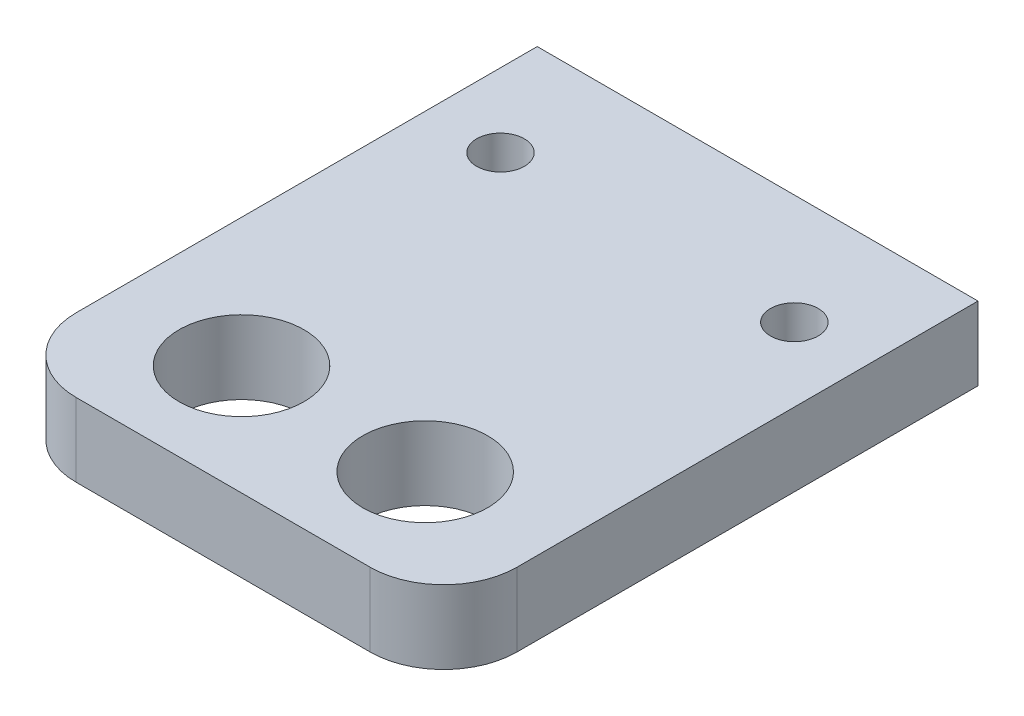
SolidWorks part; units mm, degrees
ref_plane "Front Plane" through (0, 0, 0) normal (0, 0, 1) x (1, 0, 0)
ref_plane "Top Plane" through (0, 0, 0) normal (0, 1, 0) x (1, 0, 0)
ref_plane "Right Plane" through (0, 0, 0) normal (1, 0, 0) x (0, 0, -1)
sketch "Sketch10" plane through (0, 0, 0) normal (0, 1, 0) x (1, 0, 0)
  line L16 (0, 72.75) -> (60, 72.75)
  line L17 (0, 72.75) -> (0, 0)
  line L18 (0, 0) -> (60, 0)
  line L19 (60, 72.75) -> (60, 0)
  circle A0 centre (10, 57.75) radius 3.25
  circle A1 centre (17.5, 15) radius 8.5
  circle A2 centre (50, 57.75) radius 3.25
  circle A3 centre (42.5, 15) radius 8.5
  point P6 (30, 0)
  point P9 (30, 72.75)
  dimension "D1" = 60
  dimension "D7" = 15
  dimension "D8" = 25
  dimension "D3" = 6.5
  dimension "D5" = 17
  dimension "D6" = 17
  dimension "D2" = 72.75
  dimension "D4" = 15
  dimension "D9" = 12.5
  dimension "D10" = 40
  dimension "D11" = 20
extrude "Boss-Extrude1" add sketch "Sketch10" along normal blind 10 contours A0 | A1 | A2 region at (30, 0, -38.5299)
fillet "Fillet1" radius 10 2 edges at (60, 5, 0) (0, 5, 0)
